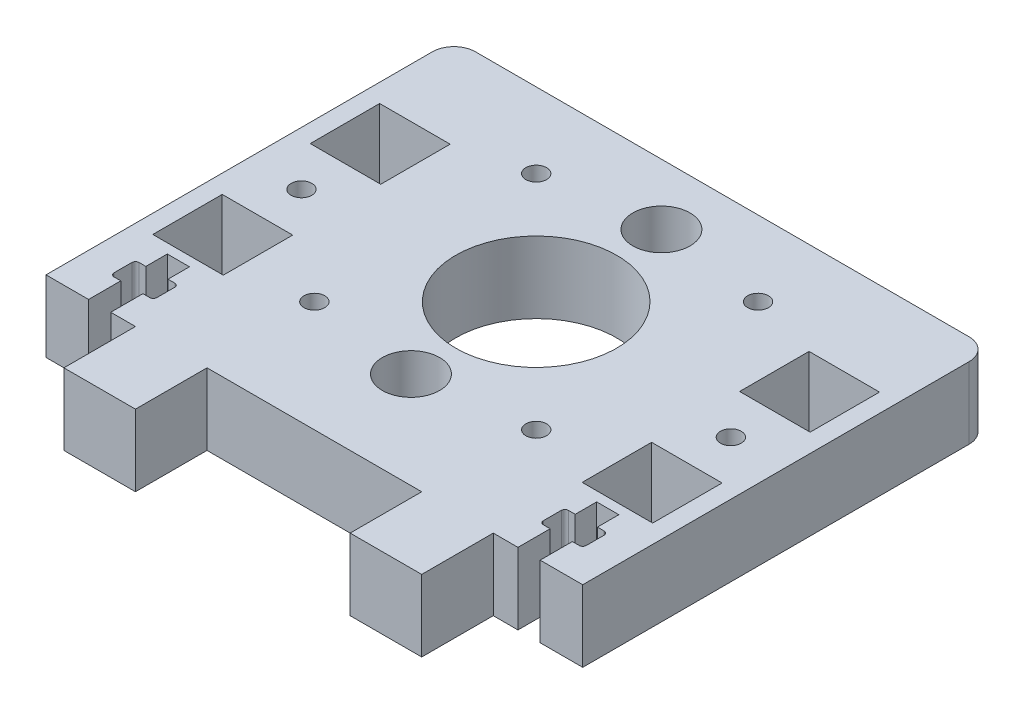
SolidWorks part; units mm, degrees
ref_plane "Front Plane" through (0, 0, 0) normal (0, 0, 1) x (1, 0, 0)
ref_plane "Top Plane" through (0, 0, 0) normal (0, 1, 0) x (1, 0, 0)
ref_plane "Right Plane" through (0, 0, 0) normal (1, 0, 0) x (0, 0, -1)
sketch "Sketch1" plane through (0, 0, 0) normal (0, 1, 0) x (1, 0, 0)
  line L0 (0, 31) -> (0, -8.5) construction
  line L1 (-34.5, 31) -> (0, 31)
  line L2 (-37.5, 28) -> (-37.5, -26)
  line L3 (-37.5, -26) -> (-25, -26)
  line L4 (0, 31) -> (0, 16.25)
  line L5 (0, -6.25) -> (0, -8.5)
  line L6 (0, -16.5) -> (0, -26) construction
  line L7 (-11.25, 5) -> (0, 5) construction
  line L8 (0, -16.5) -> (0, -26)
  line L9 (-30, 18.05) -> (-30, 8.35) construction
  line L10 (-37.5, 2.2) -> (0, 2.2) construction
  line L11 (-34.925, 18.05) -> (-25.075, 18.05)
  line L12 (-34.925, 18.05) -> (-34.925, 8.35)
  line L13 (-34.925, 8.35) -> (-25.075, 8.35)
  line L14 (-25.075, 18.05) -> (-25.075, 8.35)
  line L15 (-34.925, 18.05) -> (-25.075, 8.35) construction
  line L16 (-34.925, 8.35) -> (-25.075, 18.05) construction
  line L17 (-34.925, -3.95) -> (-25.075, -13.65) construction
  line L18 (-34.925, -13.65) -> (-25.075, -3.95) construction
  line L19 (-25.075, -13.65) -> (-25.075, -3.95)
  line L20 (-34.925, -3.95) -> (-25.075, -3.95)
  line L21 (-34.925, -13.65) -> (-34.925, -3.95)
  line L22 (-34.925, -13.65) -> (-25.075, -13.65)
  line L23 (-30, -3.95) -> (-30, -13.65) construction
  line L24 (-30, -8.8) -> (-30, 13.2) construction
  line L25 (0, 5) -> (-15.5, 20.5) construction
  line L35 (-15, -26) -> (0, -26)
  line L43 (-20, -36) -> (-20, -24.65) construction
  line L44 (-15, -26) -> (-15, -36)
  line L45 (-15, -36) -> (-25, -36)
  line L46 (-25, -36) -> (-25, -26)
  arc A1 (-34.5, 31) -> (-37.5, 28) centre (-34.5, 28) ccw
  arc A2 (0, 16.25) -> (0, -6.25) centre (0, 5) ccw
  circle A4 centre (-15.5, 20.5) radius 1.45
  circle A6 centre (-15.5, -10.5) radius 1.45
  circle A7 centre (-30, 2.2) radius 1.45
  arc A10 (0, -8.5) -> (0, -16.5) centre (0, -12.5) ccw
  point P0 (0, 0)
  point P28 (-30, 13.2)
  point P39 (-30, -8.8)
  dimension "D7" = 22.5
  dimension "D17" = 8
  dimension "D14" = 2.9
  dimension "D6" = 3
  dimension "D19" = 2.9
  dimension "D1" = 57
  dimension "D9" = 9.85
  dimension "D10" = 9.7
  dimension "D22" = 10
  dimension "D23" = 10
  dimension "D16" = 17.5
  dimension "D11" = 22
  dimension "D13" = 2.2
  dimension "D3" = 37.5
  dimension "D4" = 31
  dimension "D5" = 15.5
  dimension "D15" = 26
  dimension "D18" = 37.5
  dimension "D20" = 20
  dimension "D8" = 13.5
  dimension "D12" = 30
extrude "MainLayout" add sketch "Sketch1" along normal blind 10
sketch "Sketch2" plane through (0, 10, 0) normal (0, 1, 0) x (1, 0, 0)
  line L0 (-30, -26) -> (-30, -15) construction
  line L1 (-28.45, -21.5) -> (-28.45, -26)
  line L2 (-37.5, -26) -> (-25, -26) construction
  line L3 (-28.45, -15) -> (-31.55, -15)
  line L4 (-31.55, -15) -> (-31.55, -18)
  line L5 (-31.55, -18) -> (-32.5, -18)
  line L6 (-33, -18.5) -> (-33, -21)
  line L7 (-32.5, -21.5) -> (-31.55, -21.5)
  line L8 (-31.55, -21.5) -> (-31.55, -26)
  line L9 (-31.55, -26) -> (-28.45, -26)
  line L10 (-27.5, -21.5) -> (-28.45, -21.5)
  line L11 (-27, -18.5) -> (-27, -21)
  line L12 (-28.45, -18) -> (-27.5, -18)
  line L13 (-28.45, -15) -> (-28.45, -18)
  line L14 (0, -26) -> (0, -16.5) construction
  line L30 (-30, -26) -> (-30, -15) construction
  arc A0 (-27, -18.5) -> (-27.5, -18) centre (-27.5, -18.5) ccw
  arc A1 (-32.5, -18) -> (-33, -18.5) centre (-32.5, -18.5) ccw
  arc A2 (-27.5, -21.5) -> (-27, -21) centre (-27.5, -21) ccw
  arc A3 (-33, -21) -> (-32.5, -21.5) centre (-32.5, -21) ccw
  point P17 (0, -21.25)
  point P38 (-27, -18)
  point P41 (-33, -18)
  point P44 (-27, -21.5)
  point P47 (-33, -21.5)
  dimension "D8" = 0.5
  dimension "D1" = 1.55
  dimension "D2" = 0
  dimension "D3" = 3.5
  dimension "D5" = 11
  dimension "D6" = 3
  dimension "D4" = 8
  dimension "D7" = 30
extrude "TSlot" cut sketch "Sketch2" against normal through all
mirror "Mirror1" about plane through (0, 0, 0) normal (1, 0, 0) of "TSlot", "MainLayout"
sketch "Sketch3" plane through (0, 10, 0) normal (0, 1, 0) x (1, 0, 0)
  line L0 (0, 31) -> (0, 0) construction
  line L1 (34.5, 31) -> (-34.5, 31) construction
  line L2 (-11.25, 5) -> (11.25, 5) construction
  circle A0 centre (0, 22.5) radius 4
  circle A1 centre (0, -12.5) radius 4 construction
  circle A2 centre (0, 5) radius 11.25 construction
  dimension "D1" = 17.5
extrude "Cut-Extrude1" cut sketch "Sketch3" against normal through all
equation "\"Y-ROD-SPACING\"=75"
equation "\"Y-BED-OFFSET\"=2"
equation "\"Y-BED-ROD-INSET\"=3.5"
equation "\"T-SLOT-NUT-FILLET-RADIUS\"=0.5"
equation "\"T-SLOT-SCREW-SHAFT-RADIUS\"=1.55"
equation "\"T-SLOT-SCREW-SHAFT-CUTOUT-LENGTH\"=11"
equation "\"T-SLOT-NUT-DEPTH\"=3.5"
equation "\"T-SLOT-NUT-WIDTH\"=2.85"
equation "\"T-SLOT-NUT-END-DISTANCE\"=8"
equation "\"ACRYLIC-TAB-CUTOUT-SIZE\"=\"ACRYLIC-THICKNESS\"+\"ACRYLIC-TAB-TOLERANCE\"*2"
equation "\"ACRYLIC-TAB-WIDTH\"=\"ACRYLIC-THICKNESS\""
equation "\"ACRYLIC-M3-HOLE\"=2.9"
equation "\"SMOOTHROD-CAP-SCREW-DISTANCE\"=20"
equation "\"FRAME-WIDTH-INNER\"=370"
equation "\"NEMA17-HOLE-SPACING\"=31"
equation "\"NEMA17-CENTRAL-CUTOUT\"=22.5"
equation "\"D7@Sketch1\"=\"NEMA17-CENTRAL-CUTOUT\""
equation "\"D5@Sketch1\"=\"NEMA17-HOLE-SPACING\"/2"
equation "\"D4@Sketch1\"=\"NEMA17-HOLE-SPACING\""
equation "\"D19@Sketch1\"=\"ACRYLIC-M3-HOLE\""
equation "\"D14@Sketch1\"=\"ACRYLIC-M3-HOLE\""
equation "\"D9@Sketch1\"=\"ACRYLIC-THICKNESS\"-\"KERF\"*2"
equation "\"D10@Sketch1\"=\"ACRYLIC-TAB-WIDTH\"-\"KERF\"*4"
equation "\"D23@Sketch1\"=\"ACRYLIC-TAB-WIDTH\""
equation "\"D22@Sketch1\"=\"ACRYLIC-TAB-WIDTH\""
equation "\"D5@Sketch2\"=\"T-SLOT-SCREW-SHAFT-CUTOUT-LENGTH\""
equation "\"D4@Sketch2\"=\"T-SLOT-NUT-END-DISTANCE\""
equation "\"D3@Sketch2\"=\"T-SLOT-NUT-DEPTH\""
equation "\"D1@Sketch2\"=\"T-SLOT-SCREW-SHAFT-RADIUS\""
equation "\"D8@Sketch2\"=\"T-SLOT-NUT-FILLET-RADIUS\""
equation "\"Z-BRACKET-REACH\"=57"
equation "\"D1@Sketch1\"=\"Z-BRACKET-REACH\""
equation "\"Z-ROD-SPACING\"=17.5"
equation "\"ACRYLIC-THICKNESS\"=10"
equation "\"TOP-BRACKET-SPACING\"=40"
equation "\"SMOOTHROD-X-LENGTH\"=350"
equation "\"SMOOTHROD-Y-LENGTH\"=350"
equation "\"SMOOTHROD-Z-LENGTH\"=350"
equation "\"SMOOTHROD-TIGHTENING-HEADROOM\"=.25"
equation "\"LEADSCREW-Z-LENGTH\"=300"
equation "\"D16@Sketch1\"=\"Z-ROD-SPACING\""
equation "\"X-ROD-SPACING\"=45"
equation "\"ACRYLIC-THICKNESS2\"=4.5"
equation "\"SCREW-LENGTH-FRAME\"=\"ACRYLIC-THICKNESS\" + 10"
equation "\"SCREW-HEAD-RADIUS\"=6"
equation "\"PRINTED-X-SMOOTHROD-DIAMETER\"=8.8"
equation "\"PRINTED-X-SMOOTHROD-CUTOUT\"=10"
equation "\"PRINTED-X-BASE-HEIGHT\"=10"
equation "\"PRINTED-LM8UU-CUTOUT-SIZE\"=15.5"
equation "\"PRINTED-LM8UU-CUTOUT-LENGTH\"=24.5"
equation "\"PRINTED-X-IDLER-HEIGHT\"=16"
equation "\"PSU-MOUNTING-WIDTH\"=95"
equation "\"PSU-MOUNTING-HEIGHT\"=177"
equation "\"D1@MainLayout\"=\"ACRYLIC-THICKNESS\""
equation "\"Z-ROD-INSET\"=13.5"
equation "\"Y-BELT-TO-ROD-DISTANCE\"=20"
equation "\"SPOOL-HOLDER-ROD-SPACING\"=150"
equation "\"D8@Sketch1\"=\"Z-ROD-INSET\""
equation "\"Y-BED-SCREW-SPACING\"=209"
equation "\"Y-BED-SCREW-CUTOUT-SLOT-HEIGHT\"=2"
equation "\"ACRYLIC-TAB-TOLERANCE\"=-.05"
equation "\"SCREW-LENGTH-MOTOR\"=\"ACRYLIC-THICKNESS\" + 5"
equation "\"SCREW-LENGTH-EXTRUDER\"=28"
equation "\"ACRYLIC-X-CARRIAGE-WIDTH\"=55"
equation "\"ACRYLIC-X-CARRIAGE-HEIGHT\"=75"
equation "\"ACRYLIC-X-CARRIAGE-LM8UU-CUTOUT-WIDTH\"=24.25"
equation "\"ACRYLIC-X-CARRIAGE-SCREW-SPACING-X\"=15"
equation "\"ACRYLIC-X-CARRIAGE-SCREW-SPACING-Y\"=33"
equation "\"ACRYLIC-X-CARRIAGE-CENTER-TAB-SPACING\"=14"
equation "\"ACRYLIC-X-CARRIAGE-EXTRUDER-OFFSET\"=26"
equation "\"ACRYLIC-X-CARRIAGE-EXTRUDER-ANGLE\"=90"
equation "\"ACRYLIC-X-CARRIAGE-EXTRUDER-SHELF-DEPTH\"=\"ACRYLIC-X-CARRIAGE-EXTRUDER-OFFSET\" + 28"
equation "\"ACRYLIC-X-CARRIAGE-EXTRUDER-BRACE-SPACING\"=23"
equation "\"ACRYLIC-X-CARRIAGE-EXTRUDER-BRACE-TAB-OFFSET\"=20"
equation "\"ACRYLIC-X-CARRIAGE-EXTRUDER-BRACE-HEIGHT\"=35"
equation "\"ACRYLIC-X-CARRIAGE-EXTRUDER-BRACE-SCREW-SPACING\"=22"
equation "\"KERF\"=0.075"
equation "\"PRINTED-M3-HOLE\"=3.5"
equation "\"PRINTED-M3-NUT-AF\"=6.25"
equation "\"ACRYLIC-X-CARRIAGE-LM8UU-CUTOUT-HEIGHT\"=11.0"
equation "\"ACRYLIC-X-CARRIAGE-DUAL-WIDTH-MULTIPLIER\"=1.65"
equation "\"ACRYLIC-X-CARRIAGE-DUAL-HOTEND-SPACING\"=42"
equation "\"ACRYLIC-X-CARRIAGE-DUAL-WIDTH\"=75"
equation "\"ACRYLIC-X-CARRIAGE-DUAL-FAN-OFFSET\"=52"
equation "\"ACRYLIC-X-CARRIAGE-DUAL-FAN-HEIGHT\"=20"
equation "\"ACRYLIC-X-CARRIAGE-DUAL-HOTEND-SEPARATION\"=36"
equation "\"ACRYLIC-X-CARRIAGE-DUAL-MOUNT-PLATE-DEPTH\"=75"
equation "\"ACRYLIC-X-CARRIAGE-DUAL-MOUNT-BRACE-WIDTH\"=33"
equation "\"ACRYLIC-X-CARRIAGE-DUAL-MOUNT-SCREW-WIDTH\"=40"
equation "\"BLOWER-FAN-WIDTH\"=15"
equation "\"D1@Sketch3\"=\"Z-ROD-SPACING\""
